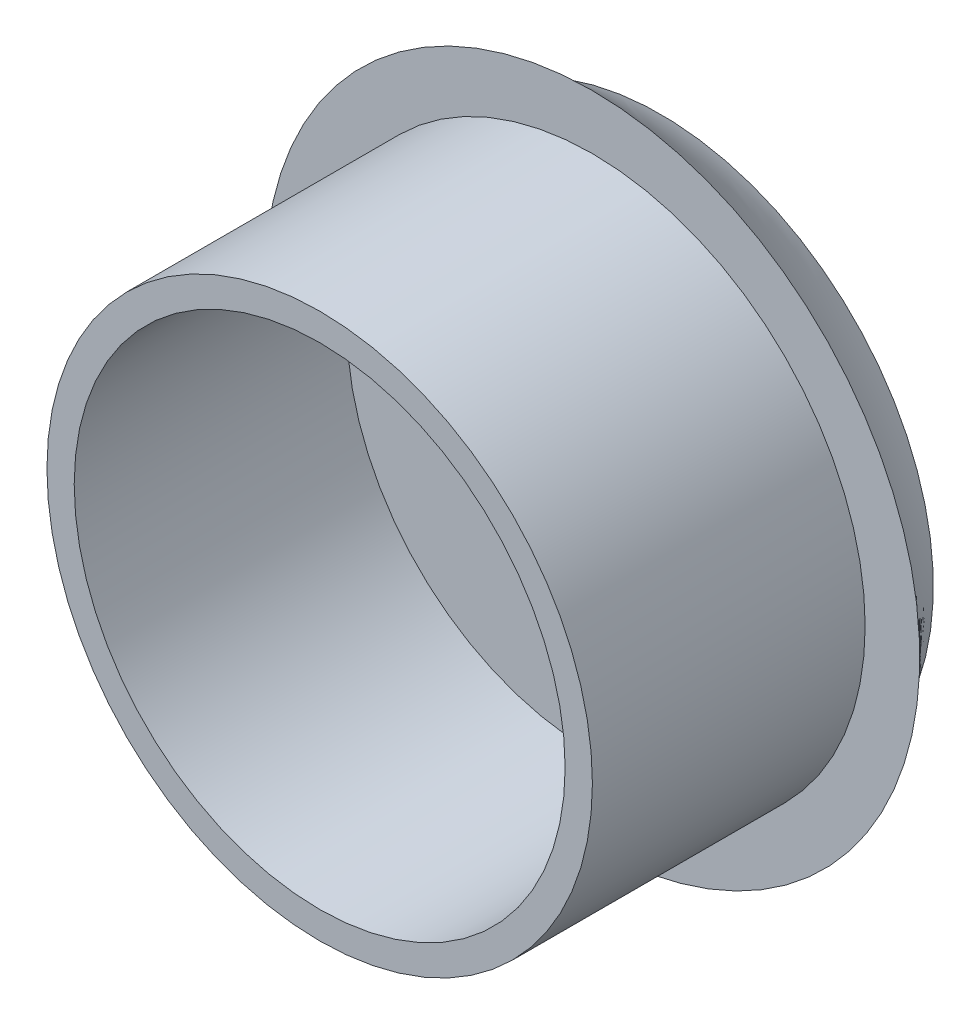
SolidWorks part; units mm, degrees
ref_plane "Front Plane" through (0, 0, 0) normal (0, 0, 1) x (1, 0, 0)
ref_plane "Top Plane" through (0, 0, 0) normal (0, 1, 0) x (1, 0, 0)
ref_plane "Right Plane" through (0, 0, 0) normal (1, 0, 0) x (0, 0, -1)
sketch "Sketch1" plane through (0, 0, 0) normal (0, 0, 1) x (1, 0, 0)
  circle A0 centre (0, 0) radius 10
  circle A1 centre (0, 0) radius 9
  dimension "D1" = 20
  dimension "D2" = 18
extrude "Boss-Extrude1" add sketch "Sketch1" along normal blind 10
sketch "Sketch2" plane through (0, 0, 0) normal (0, 0, -1) x (-1, 0, 0)
  circle A0 centre (0, 0) radius 12
  dimension "D1" = 24
ref_plane "Plane1" through (0, 0, -2.5) normal (0, 0, -1) x (-1, 0, 0)
sketch "Sketch3" plane through (0, 0, -2.5) normal (0, 0, -1) x (-1, 0, 0)
  circle A0 centre (0, 0) radius 10
  dimension "D1" = 20
loft "Loft1" add profiles "Sketch2", "Sketch3" connector at (2.0929, 11.8161, 0) connector at (-1.5023, 9.8865, -2.5)
